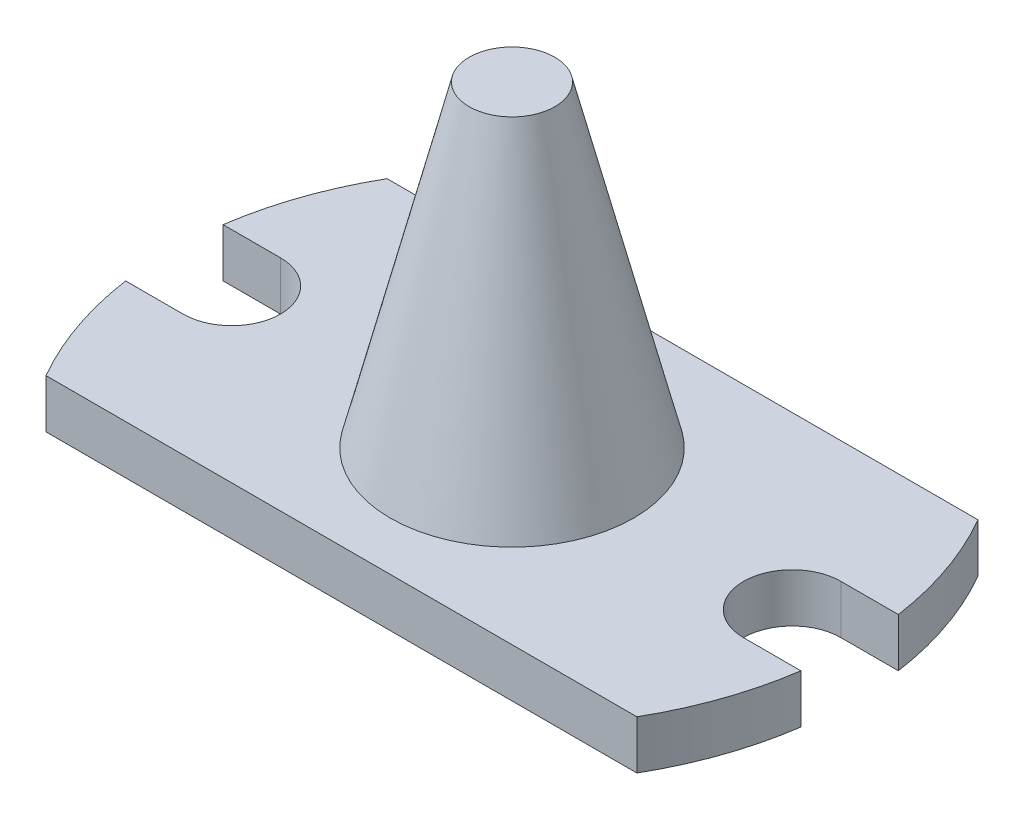
SolidWorks part; units mm, degrees
material "Plain Carbon Steel"
ref_plane "Front Plane" through (0, 0, 0) normal (0, 0, 1) x (1, 0, 0)
ref_plane "Top Plane" through (0, 0, 0) normal (0, 1, 0) x (1, 0, 0)
ref_plane "Right Plane" through (0, 0, 0) normal (1, 0, 0) x (0, 0, -1)
sketch "Sketch1" plane through (0, 0, 0) normal (0, 1, 0) x (1, 0, 0)
  line L0 (9.1225, -9.257) -> (9.1225, 60.743) construction
  line L5 (-48.3775, 60.743) -> (66.6225, 60.743)
  line L7 (-48.3775, -9.257) -> (66.6225, -9.257)
  line L9 (-48.3775, 25.743) -> (66.6225, 25.743) construction
  line L10 (66.6225, 60.743) -> (69.7443, 60.743)
  line L11 (66.6225, -9.257) -> (69.7443, -9.257)
  line L12 (-48.3775, 60.743) -> (-51.4993, 60.743)
  line L13 (-48.3775, -9.257) -> (-51.4993, -9.257)
  line L16 (-48.3775, 60.743) -> (-48.3775, -9.257) construction
  line L17 (66.6225, 60.743) -> (66.6225, -9.257) construction
  line L18 (-48.3775, 35.743) -> (-60.1596, 35.743)
  line L19 (-48.3775, 15.743) -> (-60.1596, 15.743)
  line L20 (66.6225, 35.743) -> (78.4045, 35.743)
  line L21 (66.6225, 15.743) -> (78.4045, 15.743)
  arc A0 (-51.4993, 60.743) -> (-60.1596, 35.743) centre (9.1225, 25.743) ccw
  arc A1 (69.7443, -9.257) -> (78.4045, 15.743) centre (9.1225, 25.743) ccw
  arc A2 (-48.3775, 15.743) -> (-48.3775, 35.743) centre (-48.3775, 25.743) ccw
  arc A3 (66.6225, 35.743) -> (66.6225, 15.743) centre (66.6225, 25.743) ccw
  arc A4 (78.4045, 35.743) -> (69.7443, 60.743) centre (9.1225, 25.743) ccw
  arc A5 (-60.1596, 15.743) -> (-51.4993, -9.257) centre (9.1225, 25.743) ccw
  dimension "D3" = 70
  dimension "D4" = 20
  dimension "D5" = 20
  dimension "D1" = 115
  dimension "D2" = 70
extrude "Boss-Extrude1" add sketch "Sketch1" along normal blind 10
ref_plane "Plane1" through (9.1225, 0, 0) normal (-1, 0, 0) x (0, 0, 1)
sketch "Sketch2" plane through (9.1225, 0, 0) normal (-1, 0, 0) x (0, 0, 1)
  line L0 (-25.743, 75) -> (-25.743, 10)
  line L1 (-15.743, 10) -> (-35.743, 10) construction
  line L2 (-50.743, 10) -> (-34.5367, 75)
  line L7 (-25.743, 10) -> (-50.743, 10)
  line L12 (-34.5367, 75) -> (-25.743, 75)
  dimension "D1" = 14
  dimension "D3" = 25
  dimension "D4" = 65
revolve "Revolve1" add sketch "Sketch2" angle 360 about L0
sketch "Sketch5" plane through (9.1225, 0, 0) normal (-1, 0, 0) x (0, 0, 1)
  line L0 (-62.6776, 110) -> (9.2642, 110) construction
  line L2 (-69.1065, 80) -> (9.2642, 80) construction
  line L3 (-25.743, 80) -> (-25.743, 110) construction
  circle A0 centre (-25.743, 80) radius 15
  dimension "D3" = 30
